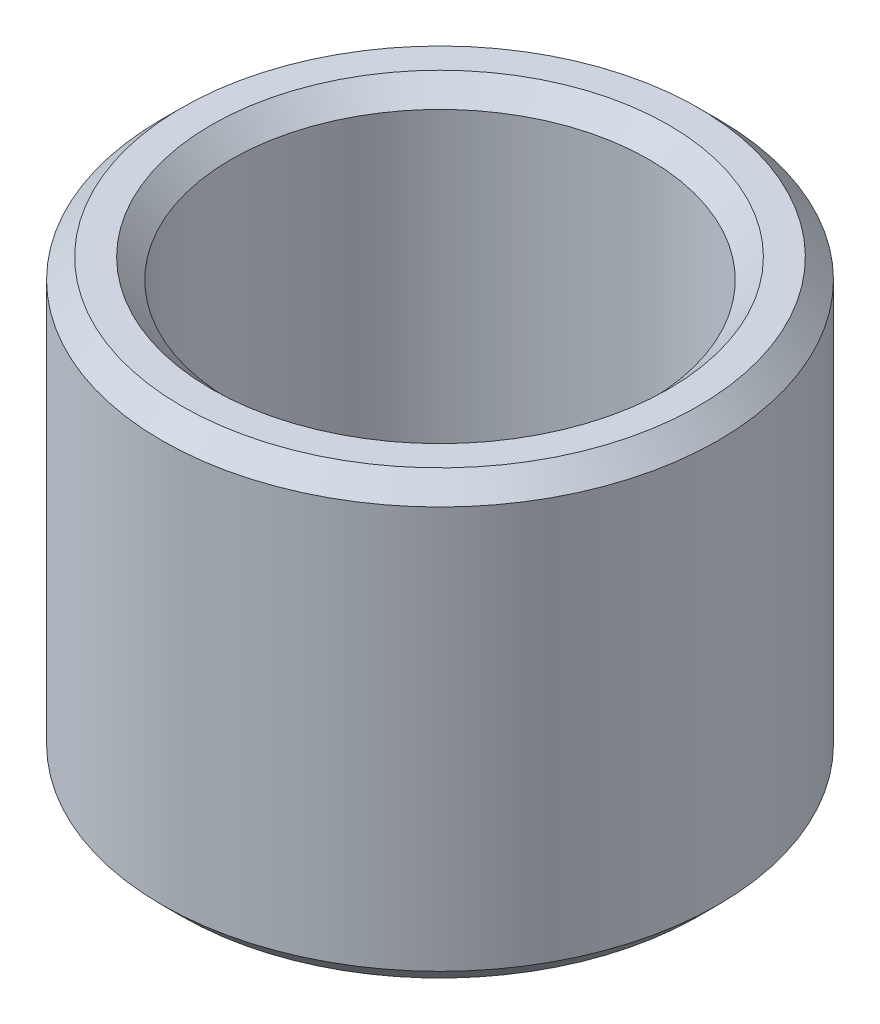
SolidWorks part; units mm, degrees
ref_plane "Front Plane" through (0, 0, 0) normal (0, 0, 1) x (1, 0, 0)
ref_plane "Top Plane" through (0, 0, 0) normal (0, 1, 0) x (1, 0, 0)
ref_plane "Right Plane" through (0, 0, 0) normal (1, 0, 0) x (0, 0, -1)
sketch "Sketch1" plane through (0, 0, 0) normal (0, 1, 0) x (1, 0, 0)
  circle A0 centre (0, 0) radius 15
  dimension "SLEEVE_OD" = 30
extrude "Boss-Extrude1" add sketch "Sketch1" along normal blind 23.8222
sketch "Sketch2" plane through (0, 0, 0) normal (0, 1, 0) x (1, 0, 0)
  circle A0 centre (0, 0) radius 11.2579
  dimension "BORE_D" = 22.5159
extrude "Cut-Extrude1" cut sketch "Sketch2" along normal through all
chamfer "Chamfer1" distance 1.0713 angle 45 4 edges at (0, 23.8222, 11.2579) (0, 0, 11.2579) (0, 0, 15) (0, 23.8222, 15)
